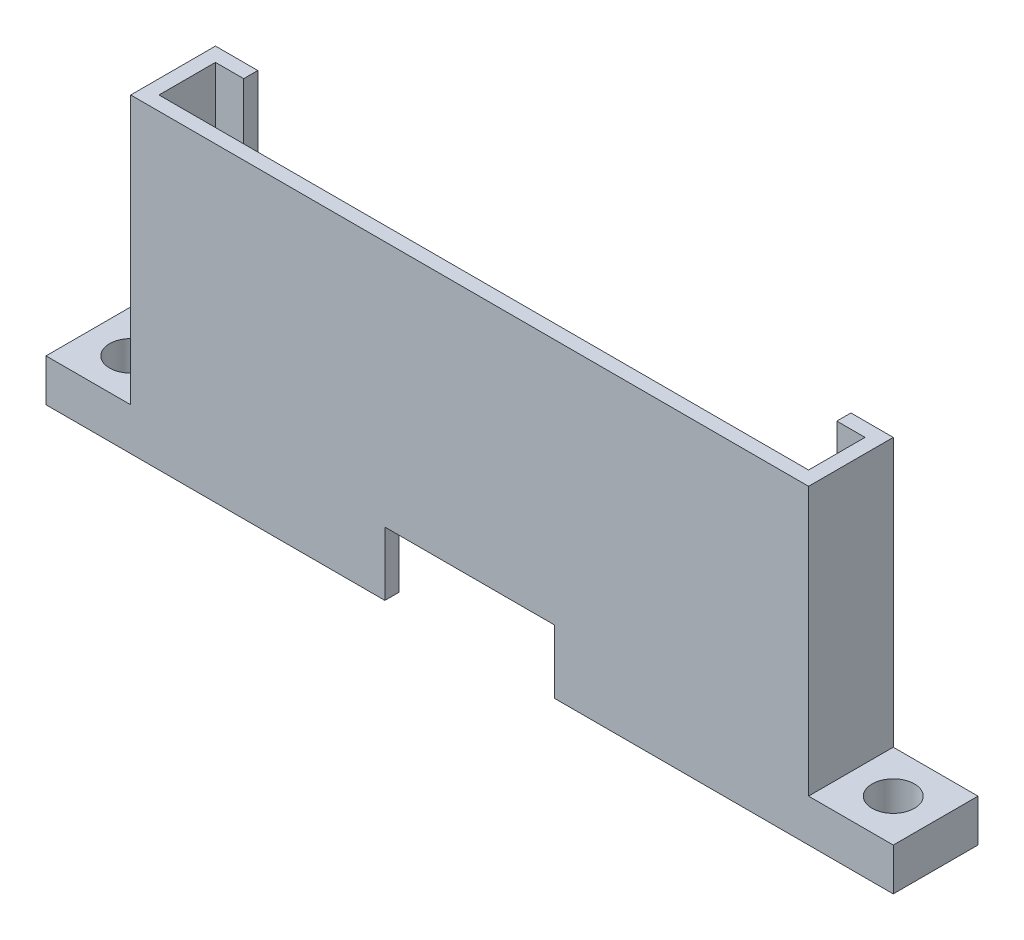
SolidWorks part; units mm, degrees
ref_plane "前基準面" through (0, 0, 0) normal (0, 0, 1) x (1, 0, 0)
ref_plane "上基準面" through (0, 0, 0) normal (0, 1, 0) x (1, 0, 0)
ref_plane "右基準面" through (0, 0, 0) normal (1, 0, 0) x (0, 0, -1)
sketch "草圖1" plane through (0, 0, 0) normal (0, 0, 1) x (1, 0, 0)
  line L1 (0, 0) -> (-48, 0)
  line L2 (0, 0) -> (0, -22)
  line L3 (0, -22) -> (-48, -22)
  line L4 (-48, 0) -> (-48, -22)
extrude "填料-伸長1" add sketch "草圖1" along normal blind 6
sketch "草圖4" plane through (0, 0, 0) normal (0, 1, 0) x (1, 0, 0)
  line L3 (-47, -5) -> (-1, -5)
  line L4 (-47, -5) -> (-47, -1)
  line L5 (-47, -1) -> (-1, -1)
  line L6 (-1, -5) -> (-1, -1)
extrude "除料-伸長2" cut sketch "草圖4" against normal blind 22
sketch "草圖5" plane through (0, 0, 0) normal (0, 1, 0) x (1, 0, 0)
  line L0 (-24, 0) -> (-24, -0.5)
  line L2 (0, 0) -> (-48, 0) construction
  line L3 (-1, -1) -> (-47, -1) construction
  line L4 (-45, 0) -> (-3, 0)
  line L5 (-45, 0) -> (-45, -1)
  line L6 (-45, -1) -> (-3, -1)
  line L7 (-3, 0) -> (-3, -1)
extrude "除料-伸長3" cut sketch "草圖5" against normal blind 22 contours L5 L4 L7 L6
sketch "草圖9" plane through (0, 0, 6) normal (0, 0, 1) x (1, 0, 0)
  line L1 (-48, -22) -> (0, -22) construction
  line L7 (-30, -17.5) -> (-18, -17.5)
  line L8 (-30, -17.5) -> (-30, -22)
  line L9 (-30, -22) -> (-18, -22)
  line L10 (-18, -17.5) -> (-18, -22)
extrude "除料-伸長5" cut sketch "草圖9" against normal blind 6 contours L8 L7 L10 L9
sketch "草圖10" plane through (0, 0, 0) normal (1, 0, 0) x (0, 0, -1)
  line L0 (0, -22) -> (0, 0) construction
  line L1 (-6, -22) -> (0, -22)
  line L2 (-6, -22) -> (-6, -19)
  line L3 (-6, -19) -> (0, -19)
  line L4 (0, -22) -> (0, -19)
extrude "填料-伸長2" add sketch "草圖10" along normal blind 6 contours L2 L1 L4 L3
sketch "草圖11" plane through (-48, 0, 0) normal (-1, 0, 0) x (0, 0, 1)
  line L0 (6, 0) -> (6, -22) construction
  line L1 (0, -22) -> (6, -22)
  line L2 (0, -22) -> (0, -19)
  line L3 (0, -19) -> (6, -19)
  line L4 (6, -22) -> (6, -19)
extrude "填料-伸長3" add sketch "草圖11" along normal blind 6 contours L2 L1 L4 L3
sketch "草圖12" plane through (0, -19, 0) normal (0, 1, 0) x (1, 0, 0)
  circle A0 centre (3, -3) radius 1.5
extrude "除料-伸長6" cut sketch "草圖12" against normal blind 3 contours A0
sketch "草圖14" plane through (0, -19, 0) normal (0, 1, 0) x (1, 0, 0)
  circle A0 centre (-51, -3) radius 1.5
extrude "除料-伸長7" cut sketch "草圖14" against normal blind 3 contours A0
